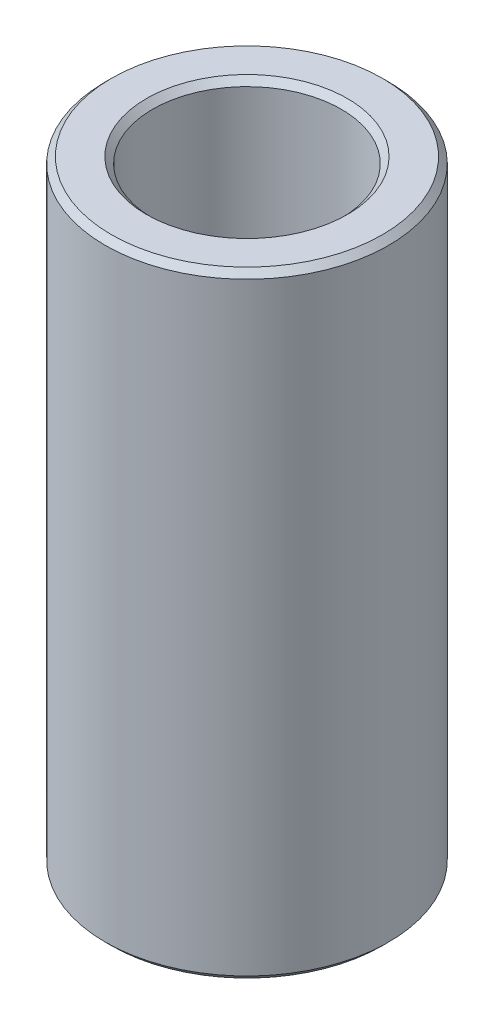
SolidWorks part; units mm, degrees
ref_plane "Front Plane" through (0, 0, 0) normal (0, 0, 1) x (1, 0, 0)
ref_plane "Top Plane" through (0, 0, 0) normal (0, 1, 0) x (1, 0, 0)
ref_plane "Right Plane" through (0, 0, 0) normal (1, 0, 0) x (0, 0, -1)
sketch "Sketch1" plane through (0, 0, 0) normal (0, 1, 0) x (1, 0, 0)
  circle A0 centre (0, 0) radius 60
  dimension "SLEEVE_OD" = 120
extrude "Boss-Extrude1" add sketch "Sketch1" along normal blind 260.7951
sketch "Sketch2" plane through (0, 0, 0) normal (0, 1, 0) x (1, 0, 0)
  circle A0 centre (0, 0) radius 39.9531
  dimension "BORE_D" = 79.9062
extrude "Cut-Extrude1" cut sketch "Sketch2" along normal through all
chamfer "Chamfer1" distance 2.6124 angle 45 4 edges at (0, 260.7951, 39.9531) (0, 0, 39.9531) (0, 0, 60) (0, 260.7951, 60)
